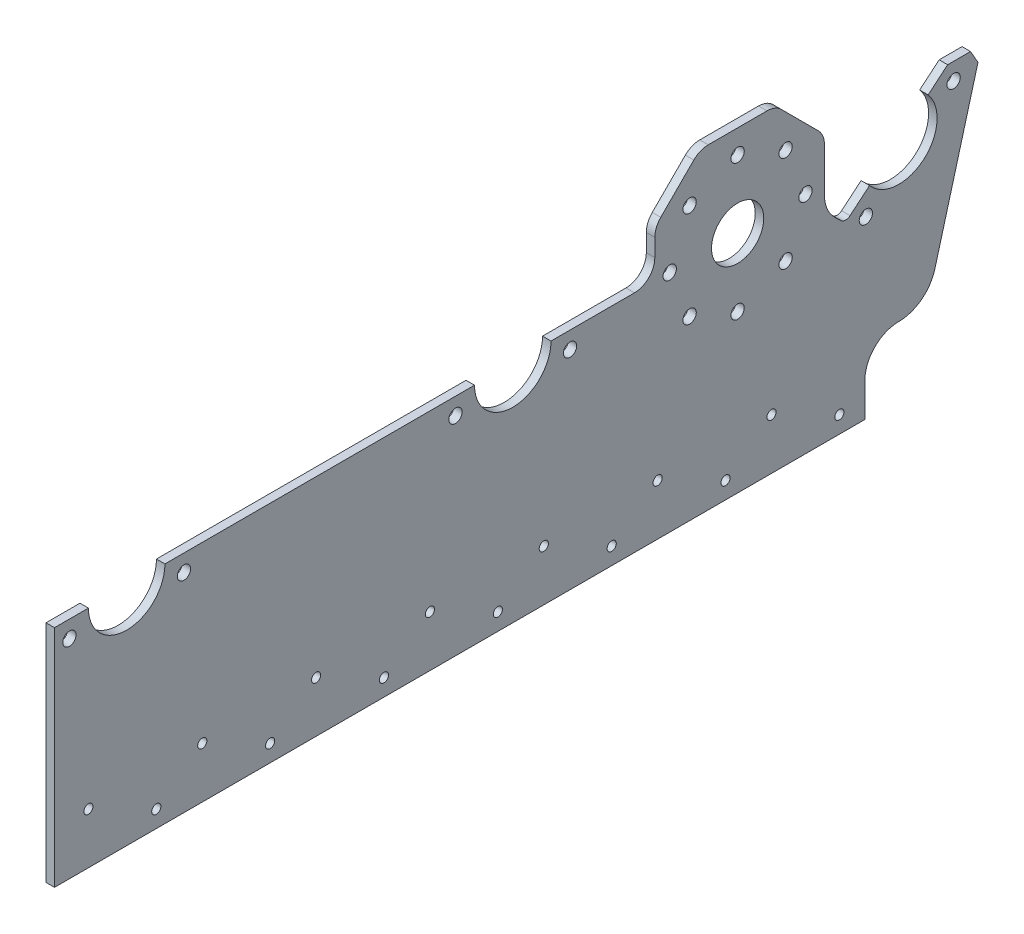
SolidWorks part; units mm, degrees
material "6061 Alloy"
ref_plane "Front Plane" through (0, 0, 0) normal (0, 0, 1) x (1, 0, 0)
ref_plane "Top Plane" through (0, 0, 0) normal (0, 1, 0) x (1, 0, 0)
ref_plane "Right Plane" through (0, 0, 0) normal (1, 0, 0) x (0, 0, -1)
sketch "Sketch1" plane through (0, 0, 0) normal (1, 0, 0) x (0, 0, -1)
  line L0 (-12.7, -12.7) -> (-315.9379, -12.7)
  line L1 (-315.9379, -12.7) -> (-315.9379, 71.4629)
  line L2 (-315.9379, 71.4629) -> (-303.2379, 71.4629)
  line L3 (-274.6121, 71.4629) -> (-158.7754, 71.4629)
  line L5 (10.9643, 80.6631) -> (18.2626, 86.7871)
  line L7 (-315.9379, 12.7) -> (13.4731, 12.7) construction
  line L8 (-12.7, -12.7) -> (-12.7, 0)
  line L9 (0, 12.4079) -> (0, 12.7) construction
  line L10 (13.4731, 22.9772) -> (30.9626, 86.7871)
  line L12 (-10.9643, 62.2627) -> (10.9643, 80.6631) construction
  line L13 (18.2626, 86.7871) -> (30.9626, 86.7871)
  line L14 (-130.1496, 71.4629) -> (-91.313, 71.4629)
  line L15 (-10.9643, 62.2627) -> (-18.2626, 56.1387)
  line L16 (-21.6532, 56.2511) -> (-23.945, 58.4485)
  line L18 (0, 71.4629) -> (-144.4625, 71.4629) construction
  line L19 (-315.9379, 15.875) -> (13.4731, 15.875) construction
  line L20 (-27.8553, 67.6154) -> (-27.8553, 87.307)
  line L21 (-27.8553, 87.307) -> (-46.1742, 105.6259)
  line L22 (-46.1742, 105.6259) -> (-74.4758, 105.6259)
  line L23 (-91.313, 88.7887) -> (-91.313, 71.4629)
  line L25 (-74.4758, 105.6259) -> (-91.313, 88.7887)
  line L26 (-144.4625, 71.4629) -> (-288.925, 71.4629) construction
  arc A3 (0, 12.7) -> (13.4731, 22.9772) centre (0, 26.67) ccw
  arc A4 (0, 12.7) -> (-12.7, 0) centre (0, 0) ccw
  circle A5 centre (0, 0) radius 12.4079 construction
  arc A6 (-303.2379, 71.4629) -> (-274.6121, 71.4629) centre (-288.925, 71.4629) ccw
  arc A7 (-158.7754, 71.4629) -> (-130.1496, 71.4629) centre (-144.4625, 71.4629) ccw
  arc A8 (-10.9643, 62.2627) -> (10.9643, 80.6631) centre (0, 71.4629) ccw
  arc A9 (-18.2626, 56.1387) -> (-21.6532, 56.2511) centre (-19.8953, 58.0845) cw
  circle A11 centre (-60.325, 71.4629) radius 9.779
  arc A14 (-27.8553, 67.6154) -> (-23.945, 58.4485) centre (-15.1553, 67.6154) ccw
  circle A15 centre (-60.325, 71.4629) radius 25.4 construction
  circle A16 centre (-60.325, 96.8629) radius 2.413
  circle A17 centre (-42.3645, 89.4234) radius 2.413
  circle A18 centre (-34.925, 71.4629) radius 2.413
  circle A19 centre (-42.3645, 53.5024) radius 2.413
  circle A20 centre (-60.325, 46.0629) radius 2.413
  circle A21 centre (-78.2855, 53.5024) radius 2.413
  circle A22 centre (-85.725, 71.4629) radius 2.413
  circle A23 centre (-78.2855, 89.4234) radius 2.413
  point P4 (-164.319, -12.7)
  point P44 (-82.018, 71.4629)
  point P51 (-27.8553, 62.1979)
  point P60 (-60.325, 71.4629)
  dimension "D1" = 25.4
  dimension "D3" = 12.7
  dimension "D5" = 28.6258
  dimension "D6" = 3.175
  dimension "D7" = 13.97
  dimension "D8" = 12.7
  dimension "D10" = 24.8158
  dimension "D13" = 9.5273
  dimension "D14" = 140
  dimension "D15" = 2.54
  dimension "D16" = 50.8
  dimension "D17" = 60.325
  dimension "D18" = 41.275
  dimension "D24" = 3.175
  dimension "D26" = 12.7
  dimension "D19" = 4.826
  dimension "D25" = 6.35
  dimension "D29" = 6.35
  dimension "D20" = 4.6567
  dimension "D30" = 9.779
  dimension "D2" = 0
  dimension "D4" = 12.7
  dimension "D9" = 12.7
  dimension "D11" = 288.925
  dimension "D12" = 288.925
  dimension "D21" = 8
  dimension "D22" = 45
  dimension "D23" = 45
  dimension "D27" = 6.35
  dimension "D28" = 3.175
extrude "Boss-Extrude1" add sketch "Sketch1" along normal blind 3.175
hole_wizard "#10 Clearance Hole1" positions "Sketch2" profile "Sketch3" hole size "#10" standard "ANSI Inch" end condition through all
sketch "Sketch2" plane through (3.175, 0, 0) normal (1, 0, 0) x (0, 0, -1)
  line L0 (-310.3562, 65.1129) -> (-267.4937, 65.1129) construction
  line L2 (-165.8937, 65.1129) -> (-123.0313, 65.1129) construction
  line L4 (-12.3356, 52.8228) -> (20.499, 80.3743) construction
  line L6 (-303.2379, 71.4629) -> (-315.9379, 71.4629) construction
  line L7 (-288.925, 65.1129) -> (-288.925, 71.4629) construction
  line L9 (-144.4625, 71.4629) -> (-144.4625, 65.1129) construction
  line L11 (0, 71.4629) -> (4.0817, 66.5985) construction
  line L14 (18.2626, 86.7871) -> (10.9643, 80.6631) construction
  line L15 (18.2626, 86.7871) -> (10.9643, 80.6631) construction
  point P0 (-310.3562, 65.1129)
  point P2 (-267.4937, 65.1129)
  point P4 (-165.8937, 65.1129)
  point P6 (-123.0313, 65.1129)
  point P8 (-12.3356, 52.8228)
  point P10 (20.499, 80.3743)
  dimension "D1" = 42.8625
  dimension "D2" = 6.35
  dimension "D3" = 6.35
sketch "Sketch3" plane through (3.175, 65.1129, 310.3562) normal (0, 1, 0) x (0, 0, -1)
  line L0 (0, 0) -> (0, 3.175)
  line L1 (0, 3.175) -> (2.4892, 3.175)
  line L2 (2.4892, 3.175) -> (2.4892, 0)
  line L5 (2.4892, 0) -> (0, 0)
  line L11 (0, -6.35) -> (0, 107.95) construction
  dimension "Thru Hole Dia." = 4.9784
  dimension "Thru Hole Depth" = 3.175
hole_wizard "#10 Clearance Hole2" positions "Sketch5" profile "Sketch6" hole size "#10" standard "ANSI Inch"
sketch "Sketch5" plane through (3.175, 0, 0) normal (1, 0, 0) x (0, 0, -1)
  point P0 (-60.325, 96.8629)
  point P3 (-42.3645, 89.4234)
  point P6 (-34.925, 71.4629)
  point P9 (-42.3645, 53.5024)
  point P12 (-60.325, 46.0629)
  point P15 (-78.2855, 53.5024)
  point P18 (-85.725, 71.4629)
  point P21 (-78.2855, 89.4234)
sketch "Sketch6" plane through (3.175, 96.8629, 60.325) normal (0, 1, 0) x (0, 0, -1)
  line L0 (0, 0) -> (0, 4.6707)
  line L1 (0, 4.6707) -> (2.4892, 3.175)
  line L2 (2.4892, 3.175) -> (2.4892, 0)
  line L5 (2.4892, 0) -> (0, 0)
  line L10 (0, 4.6707) -> (-2.4892, 3.175) construction
  line L11 (0, -6.35) -> (0, 107.95) construction
  dimension "Hole Dia." = 4.9784
  dimension "Hole Depth" = 3.175
  dimension "Drill Angle" = 118
chamfer "Chamfer1" distance 5.08 angle 45 1 edges at (1.5875, 86.7871, -30.9626) first distance on face at (1.5875, 54.8821, -22.2179)
fillet "Fillet1" radius 7.62 5 edges at (1.5875, 87.307, 27.8553) (1.5875, 105.6259, 46.1742) (1.5875, 105.6259, 74.4758) (1.5875, 88.7887, 91.313) (1.5875, 71.4629, 91.313)
hole_wizard "1/8 (0.135) Diameter Hole1" positions "Sketch7" profile "Sketch8" hole size "1/8" standard "ANSI Inch"
sketch "Sketch7" plane through (0, 0, 0) normal (-1, 0, 0) x (0, 0, 1)
  line L0 (315.9379, -12.7) -> (12.7, -12.7) construction
  line L1 (12.7, -12.7) -> (12.7, 0) construction
  line L2 (315.9379, 71.4629) -> (315.9379, -12.7) construction
  point P0 (22.2504, -6.35)
  point P2 (47.6504, 6.35)
  point P19 (64.8483, -6.35)
  point P20 (90.2483, 6.35)
  point P21 (107.4462, -6.35)
  point P22 (132.8462, 6.35)
  point P23 (150.0441, -6.35)
  point P24 (175.4441, 6.35)
  point P25 (192.6421, -6.35)
  point P26 (218.0421, 6.35)
  point P27 (235.24, -6.35)
  point P28 (260.64, 6.35)
  point P29 (277.8379, -6.35)
  point P30 (303.2379, 6.35)
  dimension "D1" = 6.35
  dimension "D2" = 25.4
  dimension "D3" = 12.7
  dimension "D4" = 9.5504
  dimension "D6" = 12.7
  dimension "D5" = 7
sketch "Sketch8" plane through (0, -6.35, 22.2504) normal (0, 1, 0) x (0, 0, 1)
  line L0 (0, 0) -> (0, 17.5402)
  line L1 (0, 17.5402) -> (1.7145, 16.51)
  line L2 (1.7145, 16.51) -> (1.7145, 0)
  line L5 (1.7145, 0) -> (0, 0)
  line L10 (0, 17.5402) -> (-1.7145, 16.51) construction
  line L11 (0, -6.35) -> (0, 107.95) construction
  dimension "Hole Dia." = 3.429
  dimension "Hole Depth" = 16.51
  dimension "Drill Angle" = 118
